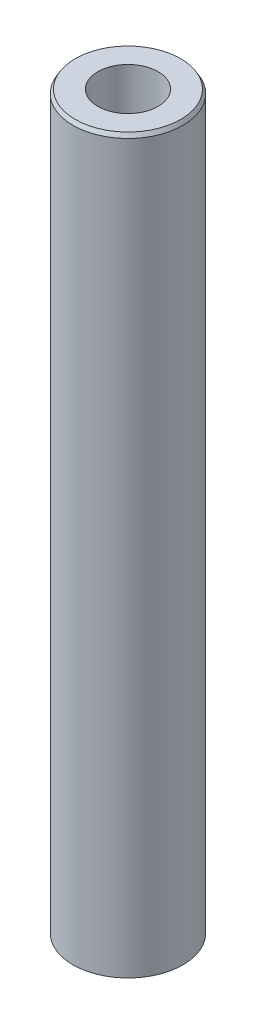
SolidWorks part; units mm, degrees
ref_plane "Front Plane" through (0, 0, 0) normal (0, 0, 1) x (1, 0, 0)
ref_plane "Top Plane" through (0, 0, 0) normal (0, 1, 0) x (1, 0, 0)
ref_plane "Right Plane" through (0, 0, 0) normal (1, 0, 0) x (0, 0, -1)
sketch "Sketch1" plane through (0, 0, 0) normal (0, 1, 0) x (1, 0, 0)
  circle A0 centre (0, 0) radius 45
  dimension "SHAFT_OD" = 90
extrude "Boss-Extrude1" add sketch "Sketch1" along normal blind 600
sketch "Sketch2" plane through (0, 0, 0) normal (0, 1, 0) x (1, 0, 0)
  circle A0 centre (0, 0) radius 24.6504
  dimension "BORE_D" = 49.3008
extrude "Cut-Extrude1" cut sketch "Sketch2" along normal through all
chamfer "Chamfer1" distance 3.2454 angle 30 2 edges at (0, 600, 45) (0, 0, 45) first distance on face at (0, 600, 45) first distance on face at (0, 0, 24.6504)
